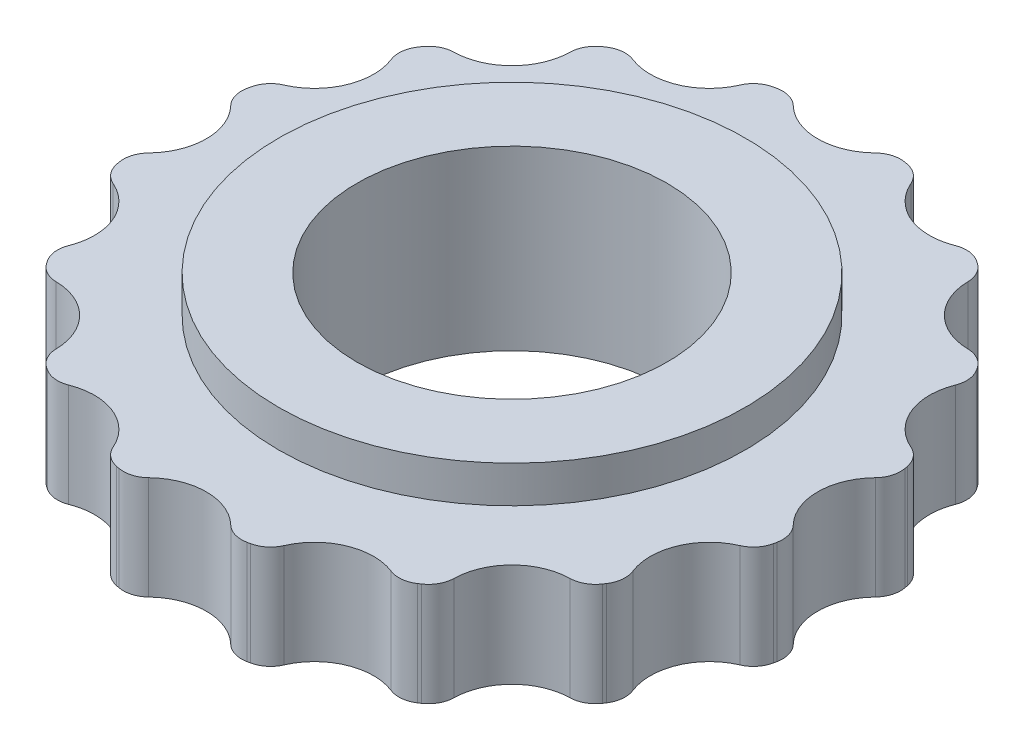
SolidWorks part; units mm, degrees
material "6061-T6 (SS)"
ref_plane "Front Plane" through (0, 0, 0) normal (0, 0, 1) x (1, 0, 0)
ref_plane "Top Plane" through (0, 0, 0) normal (0, 1, 0) x (1, 0, 0)
ref_plane "Right Plane" through (0, 0, 0) normal (1, 0, 0) x (0, 0, -1)
sketch "Sketch1" plane through (0, 0, 0) normal (0, 1, 0) x (1, 0, 0)
  circle A0 centre (0, 0) radius 22.7
  circle A1 centre (0, 0) radius 10.5
  dimension "D1" = 45.4
  dimension "D2" = 21
extrude "Boss-Extrude1" add sketch "Sketch1" along normal mid plane 12
cosmetic thread "Cosmetic Thread1" parameters "D2"=24
sketch "Sketch2" plane through (0, 6, 0) normal (0, 1, 0) x (1, 0, 0)
  circle A0 centre (0, 0) radius 15.8
  dimension "D1" = 31.6
extrude "Cut-Extrude1" cut sketch "Sketch2" against normal blind 2.5 flip side to cut
mirror "Mirror1" about plane through (0, 0, 0) normal (0, 1, 0) of "Cut-Extrude1"
fillet "Fillet1" radius 6 1 edges at (0, -3.5, 15.8)
sketch "Sketch3" plane through (0, -3.5, 0) normal (0, -1, 0) x (1, 0, 0)
  line L0 (0, 24.7) -> (0, 0) construction
  arc A0 (-2.7798, 21.8237) -> (2.7798, 21.8237) centre (0, 24.7) ccw
  circle A2 centre (0, 0) radius 22.7 construction
  arc A4 (4.3297, 22.2833) -> (2.7798, 21.8237) centre (3.9959, 20.5654) ccw
  arc A5 (-2.7798, 21.8237) -> (-4.3297, 22.2833) centre (-3.9959, 20.5654) ccw
  arc A6 (4.3297, 22.2833) -> (-4.3297, 22.2833) centre (0, 0) ccw
  point P2 (0, 20.6734)
  point P3 (0, 22.7)
  dimension "D1" = 8
  dimension "D4" = 1.75
  dimension "D2" = 2
  dimension "D3" = 24.7
extrude "Cut-Extrude2" cut sketch "Sketch3" against normal through all
pattern_circular "CirPattern1" count 16 over 360 about axis through (0, -6, 0) along (0, 1, 0) of "Cut-Extrude2"
